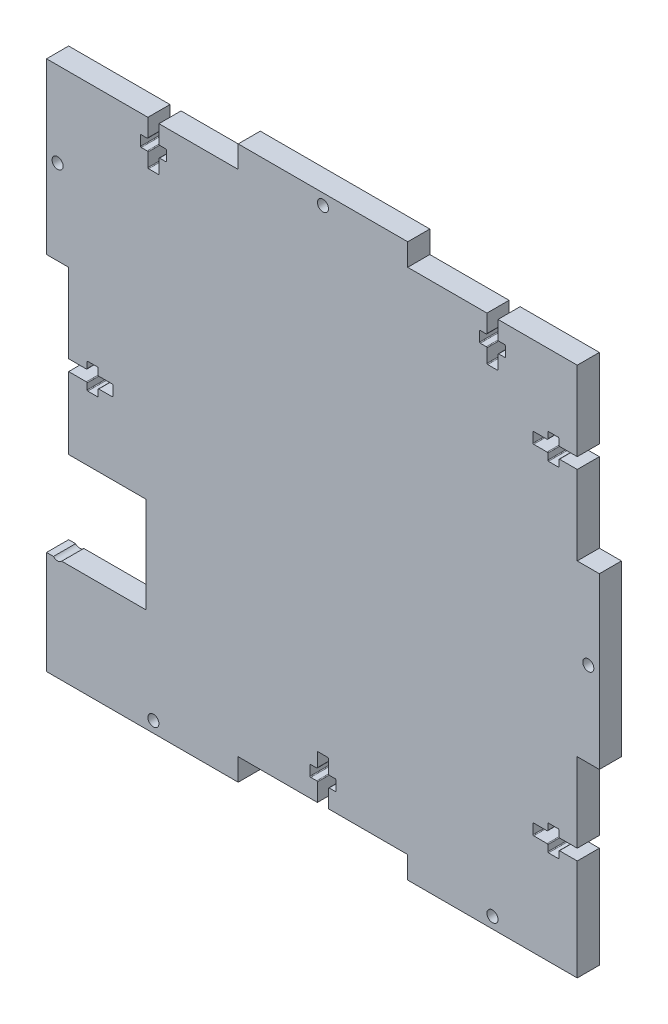
SolidWorks part; units mm, degrees
ref_plane "Front Plane" through (0, 0, 0) normal (0, 0, 1) x (1, 0, 0)
ref_plane "Top Plane" through (0, 0, 0) normal (0, 1, 0) x (1, 0, 0)
ref_plane "Right Plane" through (0, 0, 0) normal (1, 0, 0) x (0, 0, -1)
sketch "Sketch1" plane through (0, 0, 0) normal (0, 0, 1) x (1, 0, 0)
  line L0 (-69, 69) -> (-23, 69)
  line L5 (-75, -75) -> (75, -75) construction
  line L6 (-75, -75) -> (-75, 75) construction
  line L7 (-75, 75) -> (75, 75) construction
  line L8 (75, -75) -> (75, 75) construction
  line L9 (75, 23) -> (69, 23)
  line L10 (69, -23) -> (75, -23)
  line L11 (-69, -69) -> (69, -69) construction
  line L12 (-69, -69) -> (-69, 69) construction
  line L13 (-69, 69) -> (69, 69) construction
  line L14 (69, -69) -> (69, 69) construction
  line L15 (-69, -69) -> (69, 69) construction
  line L16 (69, -69) -> (69, -23)
  line L17 (-23, 69) -> (-23, 75)
  line L18 (-23, 75) -> (23, 75)
  line L19 (23, 75) -> (23, 69)
  line L20 (23, 69) -> (69, 69)
  line L21 (75, -23) -> (75, 23)
  line L22 (69, 23) -> (69, 69)
  line L23 (-75, 23) -> (-69, 23)
  line L24 (-69, 69) -> (-75, 69)
  line L25 (-75, 69) -> (-75, 23)
  line L26 (69, -69) -> (69, -75)
  line L27 (69, -75) -> (23, -75)
  line L28 (23, -75) -> (23, -69)
  line L29 (23, -69) -> (-23, -69)
  line L30 (-23, -69) -> (-23, -75)
  line L31 (-23, -75) -> (-69, -75)
  line L32 (-69, -75) -> (-69, -69) construction
  line L33 (-69, 23) -> (-69, -23)
  line L34 (-69, -23) -> (-75, -23)
  line L35 (-75, -23) -> (-75, -69)
  line L36 (-75, -69) -> (-69, -69) construction
  line L37 (-46, 69) -> (-46, -75) construction
  line L38 (-69, 69) -> (69, -69) construction
  line L39 (-75, -75) -> (-69, -75)
  line L40 (-75, -75) -> (-75, -69)
  point P0 (0, 0)
  point P6 (-7, -7)
  point P26 (0, -75)
  point P27 (-75, 0)
  dimension "D1" = 150
  dimension "D2" = 150
  dimension "D5" = 46
  dimension "D3" = 6
  dimension "D6" = 6
  dimension "D7" = 6
extrude "Box Side" add sketch "Sketch1" along normal blind 6
sketch "Sketch2" plane through (0, 0, 6) normal (0, 0, 1) x (1, 0, 0)
  line L0 (23, 72) -> (-23, 72) construction
  line L1 (23, 75) -> (23, 69) construction
  line L2 (-23, 69) -> (-23, 75) construction
  line L3 (-46, 69) -> (-46, -75) construction
  line L5 (0, 75) -> (0, 69) construction
  line L6 (-23, 75) -> (23, 75) construction
  line L7 (-69, 69) -> (69, 69) construction
  line L16 (-46, 69) -> (-46, -75) construction
  line L21 (0, -69) -> (0, 69) construction
  line L35 (-69, 69) -> (-23, 69) construction
  line L36 (-44.5, 69) -> (-44.5, 64.2)
  line L37 (-44.3, 64) -> (-42.7, 64)
  line L38 (-42.5, 63.8) -> (-42.5, 61.2)
  line L39 (-42.7, 61) -> (-44.3, 61)
  line L40 (-44.5, 60.8) -> (-44.5, 57.2)
  line L46 (-44.7, 57) -> (-47.3, 57)
  line L48 (-44.5, 69) -> (-47.5, 69)
  line L51 (-47.5, 60.8) -> (-47.5, 57.2)
  line L52 (-49.3, 61) -> (-47.7, 61)
  line L53 (-49.5, 63.8) -> (-49.5, 61.2)
  line L54 (-47.7, 64) -> (-49.3, 64)
  line L55 (-47.5, 69) -> (-47.5, 64.2)
  line L56 (47.5, 69) -> (47.5, 64.2)
  line L57 (47.7, 64) -> (49.3, 64)
  line L58 (49.5, 63.8) -> (49.5, 61.2)
  line L59 (49.3, 61) -> (47.7, 61)
  line L60 (47.5, 60.8) -> (47.5, 57.2)
  line L61 (44.5, 69) -> (47.5, 69)
  line L62 (44.7, 57) -> (47.3, 57)
  line L63 (44.5, 60.8) -> (44.5, 57.2)
  line L64 (42.7, 61) -> (44.3, 61)
  line L65 (42.5, 63.8) -> (42.5, 61.2)
  line L66 (44.3, 64) -> (42.7, 64)
  line L67 (44.5, 69) -> (44.5, 64.2)
  line L68 (-69, -69) -> (69, 69) construction
  line L69 (-69, -69) -> (69, 69) construction
  line L70 (75, 0) -> (69, 0) construction
  line L71 (72, 23) -> (72, -23) construction
  line L72 (69, 44.5) -> (64.2, 44.5)
  line L73 (64, 44.3) -> (64, 42.7)
  line L74 (63.8, 42.5) -> (61.2, 42.5)
  line L75 (61, 42.7) -> (61, 44.3)
  line L76 (60.8, 44.5) -> (57.2, 44.5)
  line L77 (57, 44.7) -> (57, 47.3)
  line L78 (69, 44.5) -> (69, 47.5)
  line L79 (60.8, 47.5) -> (57.2, 47.5)
  line L80 (61, 49.3) -> (61, 47.7)
  line L81 (63.8, 49.5) -> (61.2, 49.5)
  line L82 (64, 47.7) -> (64, 49.3)
  line L83 (69, 47.5) -> (64.2, 47.5)
  line L84 (69, -47.5) -> (64.2, -47.5)
  line L85 (64, -47.7) -> (64, -49.3)
  line L86 (63.8, -49.5) -> (61.2, -49.5)
  line L87 (61, -49.3) -> (61, -47.7)
  line L88 (60.8, -47.5) -> (57.2, -47.5)
  line L89 (69, -44.5) -> (69, -47.5)
  line L90 (57, -44.7) -> (57, -47.3)
  line L91 (60.8, -44.5) -> (57.2, -44.5)
  line L92 (61, -42.7) -> (61, -44.3)
  line L93 (63.8, -42.5) -> (61.2, -42.5)
  line L94 (64, -44.3) -> (64, -42.7)
  line L95 (69, -44.5) -> (64.2, -44.5)
  line L120 (-69, 69) -> (69, -69) construction
  line L121 (-69, 69) -> (69, -69) construction
  line L122 (-1.5, -69) -> (1.5, -69)
  line L123 (-23, -69) -> (23, -69) construction
  line L124 (1.5, -69) -> (1.5, -64.2)
  line L125 (1.7, -64) -> (3.3, -64)
  line L126 (3.5, -63.8) -> (3.5, -61.2)
  line L127 (3.3, -61) -> (1.7, -61)
  line L128 (1.5, -60.8) -> (1.5, -57.2)
  line L129 (1.3, -57) -> (-1.3, -57)
  line L130 (-1.5, -60.8) -> (-1.5, -57.2)
  line L131 (-3.3, -61) -> (-1.7, -61)
  line L132 (-3.5, -63.8) -> (-3.5, -61.2)
  line L133 (-1.7, -64) -> (-3.3, -64)
  line L134 (-1.5, -69) -> (-1.5, -64.2)
  line L135 (-69, -1.5) -> (-64.2, -1.5)
  line L136 (-64, -1.7) -> (-64, -3.3)
  line L137 (-63.8, -3.5) -> (-61.2, -3.5)
  line L138 (-61, -3.3) -> (-61, -1.7)
  line L139 (-60.8, -1.5) -> (-57.2, -1.5)
  line L140 (-57, 1.3) -> (-57, -1.3)
  line L141 (-60.8, 1.5) -> (-57.2, 1.5)
  line L142 (-61, 3.3) -> (-61, 1.7)
  line L143 (-63.8, 3.5) -> (-61.2, 3.5)
  line L144 (-64, 1.7) -> (-64, 3.3)
  line L145 (-69, 1.5) -> (-64.2, 1.5)
  line L146 (-69, -1.5) -> (-69, 1.5)
  line L147 (-69, -72) -> (-23, -72) construction
  line L148 (-23, 69) -> (-75, 69) construction
  line L149 (-23, -75) -> (-23, -69) construction
  line L150 (-69, -69) -> (-69, -75) construction
  line L151 (-75, -75) -> (-23, -75) construction
  circle A0 centre (0, 72) radius 1.5
  arc A1 (-44.5, 57.2) -> (-44.7, 57) centre (-44.7, 57.2) cw
  arc A2 (-44.3, 61) -> (-44.5, 60.8) centre (-44.3, 60.8) ccw
  arc A3 (-42.5, 61.2) -> (-42.7, 61) centre (-42.7, 61.2) cw
  arc A4 (-42.7, 64) -> (-42.5, 63.8) centre (-42.7, 63.8) cw
  arc A5 (-44.5, 64.2) -> (-44.3, 64) centre (-44.3, 64.2) ccw
  arc A6 (-47.5, 64.2) -> (-47.7, 64) centre (-47.7, 64.2) cw
  arc A7 (-49.3, 64) -> (-49.5, 63.8) centre (-49.3, 63.8) ccw
  arc A8 (-49.5, 61.2) -> (-49.3, 61) centre (-49.3, 61.2) ccw
  arc A9 (-47.7, 61) -> (-47.5, 60.8) centre (-47.7, 60.8) cw
  arc A10 (-47.5, 57.2) -> (-47.3, 57) centre (-47.3, 57.2) ccw
  arc A11 (47.5, 57.2) -> (47.3, 57) centre (47.3, 57.2) cw
  arc A12 (47.7, 61) -> (47.5, 60.8) centre (47.7, 60.8) ccw
  arc A13 (49.5, 61.2) -> (49.3, 61) centre (49.3, 61.2) cw
  arc A14 (49.3, 64) -> (49.5, 63.8) centre (49.3, 63.8) cw
  arc A15 (47.5, 64.2) -> (47.7, 64) centre (47.7, 64.2) ccw
  arc A16 (44.5, 64.2) -> (44.3, 64) centre (44.3, 64.2) cw
  arc A17 (42.7, 64) -> (42.5, 63.8) centre (42.7, 63.8) ccw
  arc A18 (42.5, 61.2) -> (42.7, 61) centre (42.7, 61.2) ccw
  arc A19 (44.3, 61) -> (44.5, 60.8) centre (44.3, 60.8) cw
  arc A20 (44.5, 57.2) -> (44.7, 57) centre (44.7, 57.2) ccw
  arc A21 (57.2, 44.5) -> (57, 44.7) centre (57.2, 44.7) cw
  arc A22 (61, 44.3) -> (60.8, 44.5) centre (60.8, 44.3) ccw
  arc A23 (61.2, 42.5) -> (61, 42.7) centre (61.2, 42.7) cw
  arc A24 (64, 42.7) -> (63.8, 42.5) centre (63.8, 42.7) cw
  arc A25 (64.2, 44.5) -> (64, 44.3) centre (64.2, 44.3) ccw
  arc A26 (64.2, 47.5) -> (64, 47.7) centre (64.2, 47.7) cw
  arc A27 (64, 49.3) -> (63.8, 49.5) centre (63.8, 49.3) ccw
  arc A28 (61.2, 49.5) -> (61, 49.3) centre (61.2, 49.3) ccw
  arc A29 (61, 47.7) -> (60.8, 47.5) centre (60.8, 47.7) cw
  arc A30 (57.2, 47.5) -> (57, 47.3) centre (57.2, 47.3) ccw
  arc A31 (57.2, -47.5) -> (57, -47.3) centre (57.2, -47.3) cw
  arc A32 (61, -47.7) -> (60.8, -47.5) centre (60.8, -47.7) ccw
  arc A33 (61.2, -49.5) -> (61, -49.3) centre (61.2, -49.3) cw
  arc A34 (64, -49.3) -> (63.8, -49.5) centre (63.8, -49.3) cw
  arc A35 (64.2, -47.5) -> (64, -47.7) centre (64.2, -47.7) ccw
  arc A36 (64.2, -44.5) -> (64, -44.3) centre (64.2, -44.3) cw
  arc A37 (64, -42.7) -> (63.8, -42.5) centre (63.8, -42.7) ccw
  arc A38 (61.2, -42.5) -> (61, -42.7) centre (61.2, -42.7) ccw
  arc A39 (61, -44.3) -> (60.8, -44.5) centre (60.8, -44.3) cw
  arc A40 (57.2, -44.5) -> (57, -44.7) centre (57.2, -44.7) ccw
  circle A41 centre (72, 0) radius 1.5
  arc A62 (1.5, -57.2) -> (1.3, -57) centre (1.3, -57.2) ccw
  arc A63 (1.7, -61) -> (1.5, -60.8) centre (1.7, -60.8) cw
  arc A64 (3.5, -61.2) -> (3.3, -61) centre (3.3, -61.2) ccw
  arc A65 (3.3, -64) -> (3.5, -63.8) centre (3.3, -63.8) ccw
  arc A66 (1.5, -64.2) -> (1.7, -64) centre (1.7, -64.2) cw
  arc A67 (-1.5, -64.2) -> (-1.7, -64) centre (-1.7, -64.2) ccw
  arc A68 (-3.3, -64) -> (-3.5, -63.8) centre (-3.3, -63.8) cw
  arc A69 (-3.5, -61.2) -> (-3.3, -61) centre (-3.3, -61.2) cw
  arc A70 (-1.7, -61) -> (-1.5, -60.8) centre (-1.7, -60.8) ccw
  arc A71 (-1.5, -57.2) -> (-1.3, -57) centre (-1.3, -57.2) cw
  arc A72 (-57.2, -1.5) -> (-57, -1.3) centre (-57.2, -1.3) ccw
  arc A73 (-61, -1.7) -> (-60.8, -1.5) centre (-60.8, -1.7) cw
  arc A74 (-61.2, -3.5) -> (-61, -3.3) centre (-61.2, -3.3) ccw
  arc A75 (-64, -3.3) -> (-63.8, -3.5) centre (-63.8, -3.3) ccw
  arc A76 (-64.2, -1.5) -> (-64, -1.7) centre (-64.2, -1.7) cw
  arc A77 (-64.2, 1.5) -> (-64, 1.7) centre (-64.2, 1.7) ccw
  arc A78 (-64, 3.3) -> (-63.8, 3.5) centre (-63.8, 3.3) cw
  arc A79 (-61.2, 3.5) -> (-61, 3.3) centre (-61.2, 3.3) cw
  arc A80 (-61, 1.7) -> (-60.8, 1.5) centre (-60.8, 1.7) ccw
  arc A81 (-57.2, 1.5) -> (-57, 1.3) centre (-57.2, 1.3) cw
  circle A82 centre (-46, -72) radius 1.5
  circle A83 centre (46, -72) radius 1.5
  circle A84 centre (-72, 46) radius 1.5
  circle A85 centre (-72, -46) radius 1.5
  point P6 (0, 72)
  point P38 (0, 0)
  point P56 (-46, 57)
  point P88 (46, 57)
  point P161 (57, 46)
  point P162 (57, -46)
  point P198 (0, -57)
  point P231 (-57, 0)
  point P234 (-42.5, 62.5)
  dimension "D1" = 3
  dimension "D2" = 0.2
  dimension "D8" = 0.2
  dimension "D14" = 3
  dimension "D4" = 3
  dimension "D7" = 1.5
  dimension "D10" = 3
  dimension "D12" = 1.5
  dimension "D9" = 12
  dimension "D11" = 5
  dimension "D13" = 7
  dimension "D3" = 12
  dimension "D5" = 7
  dimension "D6" = 5
extrude "Screw Cut-outs" cut sketch "Sketch2" against normal through all
sketch "Sketch3" plane through (0, 0, 6) normal (0, 0, 1) x (1, 0, 0)
  line L0 (-75, -75) -> (-23, -75) construction
  line L1 (-75, -47) -> (-48, -47)
  line L2 (-75, -47) -> (-75, -21)
  line L3 (-75, -21) -> (-48, -21)
  line L4 (-48, -47) -> (-48, -21)
  line L5 (-75, -23) -> (-75, -75) construction
  dimension "D1" = 28
  dimension "D2" = 27
  dimension "D3" = 26
extrude "Cut-Extrude1" cut sketch "Sketch3" against normal through all
equation "\"filletRadius\"=0.2"
equation "\"D8@Sketch2\"=\"filletRadius\""
equation "\"D2@Sketch2\"=\"filletRadius\""
equation "\"fingerWidth\"= 46"
equation "\"D5@Sketch1\"=\"fingerWidth\""
equation "\"wallThickness\"= 6"
equation "\"D3@Sketch1\" = \"wallThickness\""
equation "\"D6@Sketch1\" = \"wallThickness\""
equation "\"D7@Sketch1\" = \"wallThickness\""
equation "\"D1@Box Side\" = \"wallThickness\""
equation "\"M3\"= 3"
equation "\"D14@Sketch2\"=\"M3\""
equation "\"D1@Sketch2\"=\"M3\""
equation "\"D12@Sketch2\"=\"M3\"/2"
equation "\"nutThickness\"=3"
equation "\"D10@Sketch2\" = \"nutThickness\""
equation "\"boltLength\"= 12"
equation "\"D9@Sketch2\" = \"boltLength\""
equation "\"distanceToNut\"= 5"
equation "\"D11@Sketch2\" = \"distanceToNut\""
equation "\"D13@Sketch2\" = \"nutWidth\""
equation "\"D7@Sketch2\"=\"M3\"/2"
equation "\"D4@Sketch2\" = \"nutThickness\""
equation "\"D3@Sketch2\" = \"boltLength\""
equation "\"D5@Sketch2\" = \"nutWidth\""
equation "\"D6@Sketch2\" = \"distanceToNut\""
equation "\"sideLength\"=150"
equation "\"D1@Sketch1\"=\"sideLength\""
equation "\"D2@Sketch1\"=\"sideLength\""
equation "\"nutWidth\"=7"
